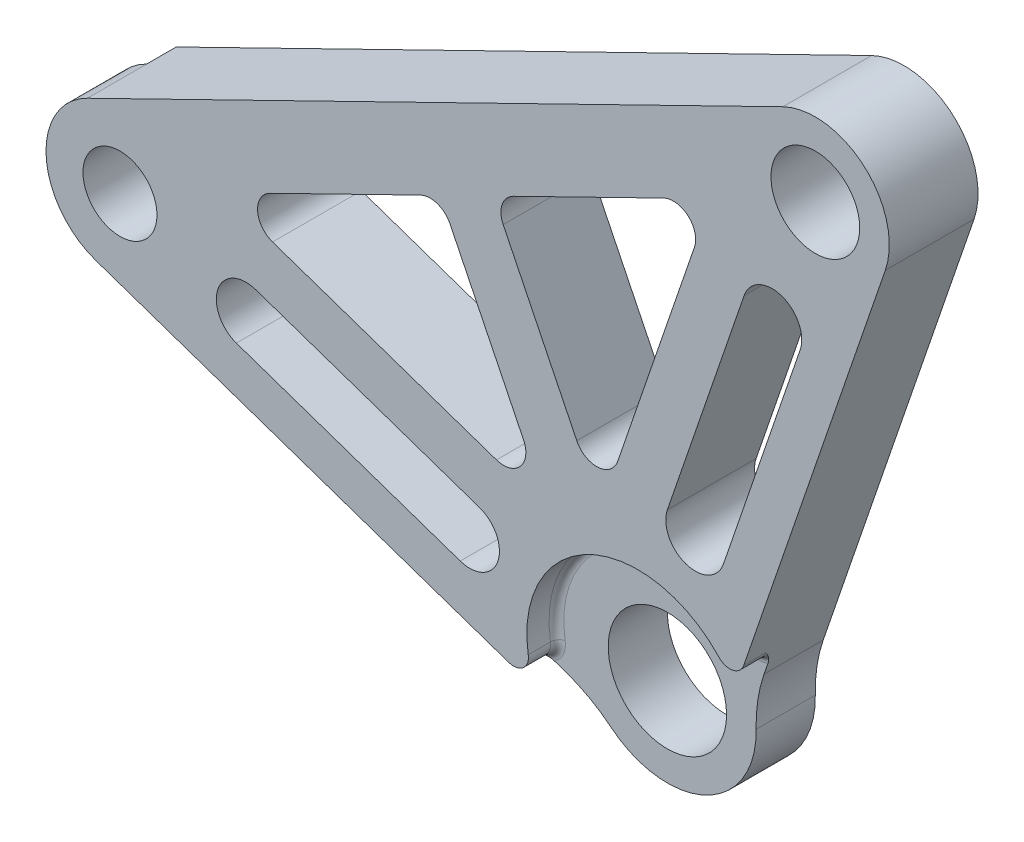
SolidWorks part; units mm, degrees
material "AISI 1045 Steel, cold drawn"
ref_plane "Front Plane" through (0, 0, 0) normal (0, 0, 1) x (1, 0, 0)
ref_plane "Top Plane" through (0, 0, 0) normal (0, 1, 0) x (1, 0, 0)
ref_plane "Right Plane" through (0, 0, 0) normal (1, 0, 0) x (0, 0, -1)
sketch "Sketch1" plane through (0, 0, 0) normal (0, 0, 1) x (1, 0, 0)
  line L2 (0, 0) -> (-35, 12) construction
  line L3 (0, 32.1948) -> (0, -15.8001) construction
  line L4 (16.7297, 33.3784) -> (6.5355, 3.6452)
  line L5 (0, 0) -> (12, 35) construction
  line L6 (-36.6216, 7.2703) -> (-6.8884, -2.924)
  line L7 (9.8022, 39.4911) -> (-37.1978, 16.4911)
  circle A1 centre (-35, 12) radius 2.5
  arc A2 (-37.1978, 16.4911) -> (-36.6216, 7.2703) centre (-35, 12) ccw
  circle A3 centre (0, 0) radius 4
  arc A5 (-6.8884, -2.924) -> (-3.7994, -4.6438) centre (-10.1317, -12.3834) cw
  circle A6 centre (12, 35) radius 3
  arc A7 (-3.7994, -4.6438) -> (5.9981, 0.1507) centre (0, 0) ccw
  arc A8 (5.9981, 0.1507) -> (6.5355, 3.6452) centre (15.995, 0.4019) cw
  arc A9 (16.7297, 33.3784) -> (9.8022, 39.4911) centre (12, 35) ccw
  dimension "D4" = 5
  dimension "D6" = 8
  dimension "D10" = 6
  dimension "D13" = 6
  dimension "D15" = 5
  dimension "D5" = 5
  dimension "D7" = 10
  dimension "D8" = 10
  dimension "D3" = 35
  dimension "D9" = 12
  dimension "D2" = 35
  dimension "D11" = 12
extrude "Boss-Extrude1" add sketch "Sketch1" along normal blind 6 contours A1 | A3 | A6 | L7 A2 L6 A5 A7 A8 L4 A9 region at (-35, 12, 0) region at (0, 0, 0) region at (12, 35, 0)
sketch "Sketch2" plane through (0, 0, 6) normal (0, 0, 1) x (1, 0, 0)
  line L0 (-24.8592, 17.0976) -> (-14.6971, 22.0705)
  line L1 (-12.6904, 21.3825) -> (-7.7175, 11.2204)
  line L2 (-9.5513, 9.1421) -> (-24.6864, 14.3313)
  line L3 (0, 0) -> (-17.0487, 34.8386) construction
  line L4 (-26.4865, 9.0811) -> (-11.3514, 3.8919) construction
  line L5 (9.8022, 39.4911) -> (-37.1978, 16.4911) construction
  line L6 (-25.8378, 10.973) -> (-10.7027, 5.7838)
  line L7 (-33.1957, 11.3814) -> (1.8043, -0.6186) construction
  line L8 (-36.6216, 7.2703) -> (-6.8884, -2.924) construction
  line L12 (-27.1351, 7.1892) -> (-12, 2)
  line L13 (-25.5935, 11.6856) -> (-19.6733, 28.9527) construction
  line L14 (-10.4555, 6.5048) -> (-3.0085, 28.2253) construction
  line L15 (-9.0976, 23.1408) -> (-4.1246, 12.9786)
  line L16 (1.7526, 30.1204) -> (-8.4096, 25.1474)
  line L17 (-1.3583, 13.1514) -> (3.8308, 28.2866)
  line L18 (9.0811, 26.4865) -> (3.8919, 11.3514) construction
  line L19 (7.1892, 27.1351) -> (2, 12)
  line L20 (10.973, 25.8378) -> (5.7838, 10.7027)
  arc A0 (-7.7175, 11.2204) -> (-9.5513, 9.1421) centre (-9.0648, 10.561) cw
  arc A1 (-24.8592, 17.0976) -> (-24.6864, 14.3313) centre (-24.1999, 15.7502) ccw
  arc A2 (-14.6971, 22.0705) -> (-12.6904, 21.3825) centre (-14.0378, 20.7232) cw
  arc A6 (-25.8378, 10.973) -> (-27.1351, 7.1892) centre (-26.4865, 9.0811) ccw
  arc A7 (-12, 2) -> (-10.7027, 5.7838) centre (-11.3514, 3.8919) ccw
  arc A8 (-8.4096, 25.1474) -> (-9.0976, 23.1408) centre (-7.7502, 23.8001) ccw
  arc A9 (-4.1246, 12.9786) -> (-1.3583, 13.1514) centre (-2.7773, 13.6379) ccw
  arc A10 (1.7526, 30.1204) -> (3.8308, 28.2866) centre (2.4119, 28.7731) cw
  arc A11 (7.1892, 27.1351) -> (10.973, 25.8378) centre (9.0811, 26.4865) cw
  arc A12 (5.7838, 10.7027) -> (2, 12) centre (3.8919, 11.3514) cw
  point P8 (-13.6978, 27.9911)
  point P17 (-18.9189, 6.4865)
  point P41 (6.4865, 18.9189)
  dimension "D4" = 1.5
  dimension "D3" = 2
  dimension "D1" = 2
  dimension "D2" = 12
  dimension "D5" = 16
extrude "Cut-Extrude1" cut sketch "Sketch2" against normal through all both and the other way through all
sketch "Sketch4" plane through (0, 0, 6) normal (0, 0, 1) x (1, 0, 0)
  circle A0 centre (0, 0) radius 7.5
  circle A1 centre (-35, 12) radius 5
  circle A2 centre (-35, 12) radius 2.5 construction
  arc A3 (-37.1978, 16.4911) -> (-36.6216, 7.2703) centre (-35, 12) ccw construction
  dimension "D1" = 15
extrude "Cut-Extrude2" cut sketch "Sketch4" against normal blind 2 contours A0
fillet "Fillet1" radius 1 2 edges at (6.5428, 3.6664, 5) (-6.9096, -2.9167, 5)
fillet "Fillet2" radius 0.5 3 edges at (-7.7476, -2.1161, 4) (-3.2966, 6.7366, 4) (6.4248, 4.8193, 4)
sketch "Sketch5" plane through (0, 0, 0) normal (0, 0, -1) x (-1, 0, 0)
  circle A0 centre (35, 12) radius 5
  dimension "D1" = 10
extrude "Cut-Extrude4" cut sketch "Sketch5" against normal blind 2 contours A0
equation "\"D8@Sketch1\"=\"D7@Sketch1\""
equation "\"D5@Sketch1\"=\"D15@Sketch1\""
